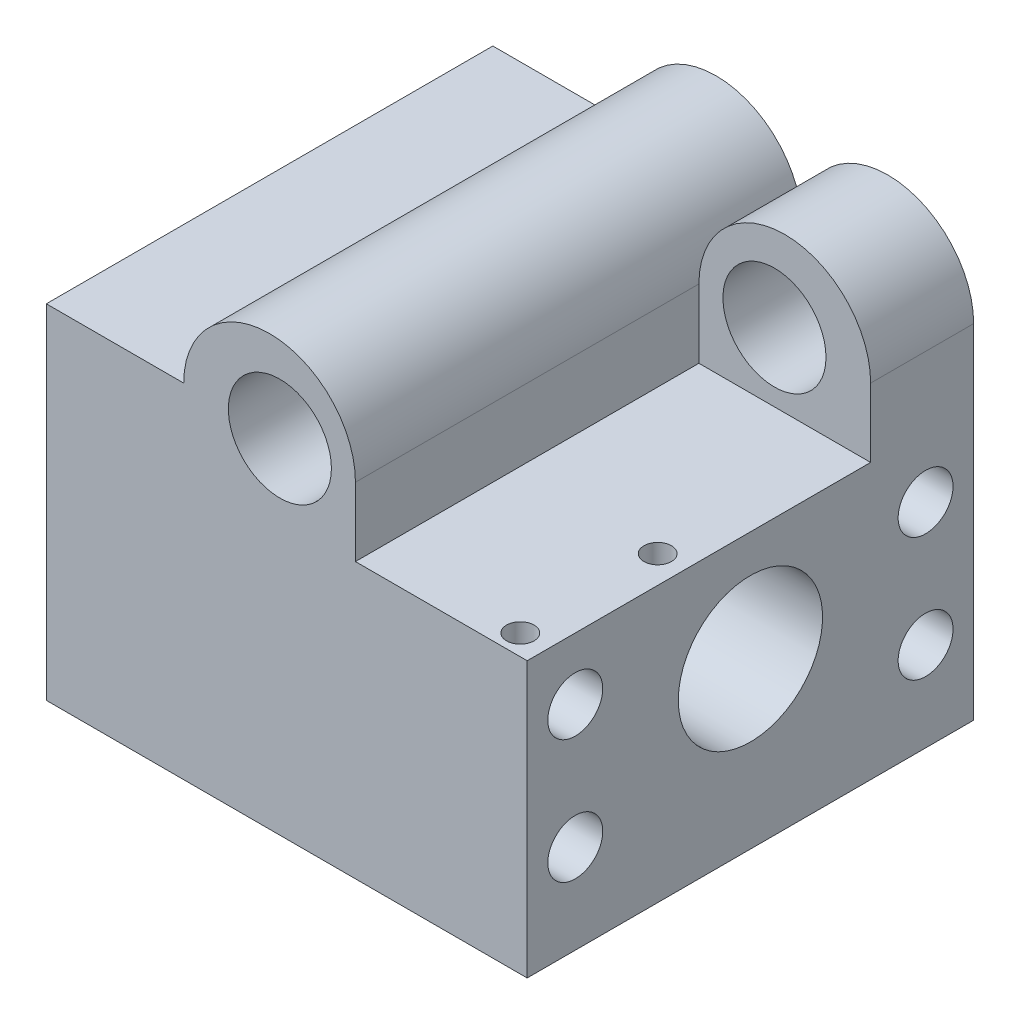
SolidWorks part; units mm, degrees
material "ABS"
ref_plane "Front Plane" through (0, 0, 0) normal (0, 0, 1) x (1, 0, 0)
ref_plane "Top Plane" through (0, 0, 0) normal (0, 1, 0) x (1, 0, 0)
ref_plane "Right Plane" through (0, 0, 0) normal (1, 0, 0) x (0, 0, -1)
sketch "Sketch1" plane through (0, 0, 0) normal (0, 0, 1) x (1, 0, 0)
  line L0 (0, 0) -> (50, 0)
  line L1 (50, 0) -> (50, 50)
  line L2 (0, 50) -> (0, 0)
  arc A0 (50, 50) -> (25, 58.6603) centre (36, 50) ccw
  arc A1 (25, 58.6603) -> (0, 50) centre (14, 50) ccw
  circle A2 centre (36, 50) radius 7.5
  circle A3 centre (14, 50) radius 7.5
  dimension "D2" = 22
  dimension "D5" = 15
  dimension "D1" = 50
  dimension "D4" = 50
extrude "Boss-Extrude1" add sketch "Sketch1" along normal blind 15
sketch "Sketch2" plane through (0, 0, 15) normal (0, 0, 1) x (1, 0, 0)
  line L0 (0, 0) -> (0, 50)
  line L4 (25, 50) -> (25, 0)
  line L6 (38, 0) -> (50, 0)
  line L7 (50, 0) -> (50, 50)
  line L8 (0, 0) -> (50, 0)
  circle A1 centre (14, 50) radius 7.5
  circle A2 centre (36, 50) radius 7.5 construction
  circle A3 centre (14, 50) radius 7.5 construction
  arc A4 (0, 50) -> (25, 50) centre (12.5, 50) cw
  arc A5 (50, 50) -> (25, 50) centre (37.5, 50) ccw
  circle M5 centre (14, 50) radius 7.5
  line M6 (0, 50) -> (0, 0)
  line M7 (0, 0) -> (50, 0)
  arc M9 (50, 50) -> (25, 58.6603) centre (36, 50) ccw
  arc M10 (25, 58.6603) -> (0, 50) centre (14, 50) ccw
extrude "Boss-Extrude2" add sketch "Sketch2" along normal blind 50 contours A4 L4 M6 M7 M5 region at (12.299, 27.2902, 15)
sketch "Sketch3" plane through (0, 0, 0) normal (0, 0, -1) x (-1, 0, 0)
  line L0 (0, 50) -> (0, 0) construction
  line L1 (-50, 0) -> (0, 0)
  line L2 (-50, 0) -> (-50, 40)
  line L3 (-50, 40) -> (0, 40)
  line L4 (0, 0) -> (0, 40)
  dimension "D1" = 40
extrude "Boss-Extrude3" add sketch "Sketch3" against normal blind 65
extrude "Cut-Extrude2" cut sketch "Sketch2<3>" against normal through all contours A5 A4 M9 M10 region at (9.5874, 62.7381, 15)
sketch "Sketch2<3>" plane through (0, 0, 15) normal (0, 0, 1) x (1, 0, 0) same geometry as "Sketch2"
sketch "Sketch9" plane through (0, 0, 0) normal (-1, 0, 0) x (0, 0, 1)
  line L0 (0, 50) -> (0, 0) construction
  line L1 (65, 50) -> (65, 0) construction
  line L2 (65, 0) -> (0, 0) construction
  line L3 (65, 0) -> (0, 0) construction
  line L4 (65, 40) -> (65, 0) construction
  circle A0 centre (58, 13) radius 4
  circle A1 centre (7, 13) radius 4
  circle A3 centre (7, 31) radius 4
  circle A4 centre (58, 31) radius 4
  circle A5 centre (32.5, 24) radius 10.5
  dimension "D1" = 8
  dimension "D2" = 13
  dimension "D3" = 7
  dimension "D4" = 7
  dimension "D5" = 18
  dimension "D6" = 21
  dimension "D7" = 24
  dimension "D8" = 32.5
extrude "Cut-Extrude3" cut sketch "Sketch9" against normal through all
sketch "Esquisse1" plane through (0, 40, 0) normal (0, 1, 0) x (1, 0, 0)
  line L0 (50, -65) -> (50, -15) construction
  line L1 (25, -65) -> (50, -65) construction
  circle A0 centre (46, -42) radius 2
  circle A1 centre (46, -62) radius 2
  dimension "D1" = 4
  dimension "D2" = 4
  dimension "D3" = 20
  dimension "D4" = 3
  dimension "D5" = 4
extrude "Enlèv. mat.-Extru.1" cut sketch "Esquisse1" against normal blind 10
sketch "Esquisse3" plane through (0, 0, 0) normal (-1, 0, 0) x (0, 0, 1)
  line L1 (11.5, 44) -> (53.5, 44)
  line L2 (11.5, 44) -> (11.5, 2)
  line L3 (11.5, 2) -> (53.5, 2)
  line L4 (53.5, 44) -> (53.5, 2)
  line L6 (65, 50) -> (65, 0) construction
  line L8 (0, 50) -> (65, 50)
  line L10 (0, 50) -> (0, 0)
  line L11 (0, 0) -> (65, 0)
  line L12 (65, 50) -> (65, 0)
  circle A0 centre (32.5, 24) radius 10.5 construction
  circle A1 centre (32.5, 24) radius 11
  circle A2 centre (17, 38.5) radius 1.5
  circle A3 centre (48, 38.5) radius 1.5
  circle A4 centre (48, 7.5) radius 1.5
  circle A5 centre (17, 7.5) radius 1.5
  circle M7 centre (58, 31) radius 4
  circle M8 centre (7, 31) radius 4
  circle M9 centre (7, 13) radius 4
  circle M10 centre (58, 13) radius 4
  line M11 (0, 50) -> (0, 0)
  line M12 (0, 0) -> (65, 0)
  line M13 (65, 0) -> (65, 50)
  line M14 (65, 50) -> (0, 50)
  dimension "D4" = 22
  dimension "D5" = 22
  dimension "D6" = 3
  dimension "D8" = 5.5
  dimension "D1" = 42
  dimension "D2" = 42
  dimension "D3" = 11.5
  dimension "D7" = 5.5
  dimension "D9" = 2
  dimension "D10" = 2
extrude "Boss.-Extru.1" add sketch "Esquisse3" along normal blind 5 contours L1 L4 L3 L2 M14 M11 M12 M13 M8 M10 M9 M7 | M10 | M7 | M8 | M9 | L4 L1 L2 L3 A5 A4 A3 A2 A1 region at (0, 43.406, 32.5) region at (0, 49.1799, 32.5) region at (0, 31, 58) region at (0, 31, 7) region at (0, 13, 7) region at (0, 13, 58)
extrude "Boss.-Extru.2" add sketch "Esquisse3<4>" along normal blind 20 contours L1 L4 L3 L2 M14 M11 M12 M13 M8 M10 M9 M7 | M7 | M10 | M8 | M9 region at (0, 49.1799, 32.5) region at (0, 31, 58) region at (0, 31, 7) region at (0, 13, 7) region at (0, 13, 58)
sketch "Esquisse3<4>" plane through (0, 0, 0) normal (-1, 0, 0) x (0, 0, 1) same geometry as "Esquisse3"
extrude "Enlèv. mat.-Extru.4" cut sketch "Esquisse3<5>" against normal blind 20 contours A3 | A4 | A5 | A2
sketch "Esquisse3<5>" plane through (0, 0, 0) normal (-1, 0, 0) x (0, 0, 1) same geometry as "Esquisse3"
